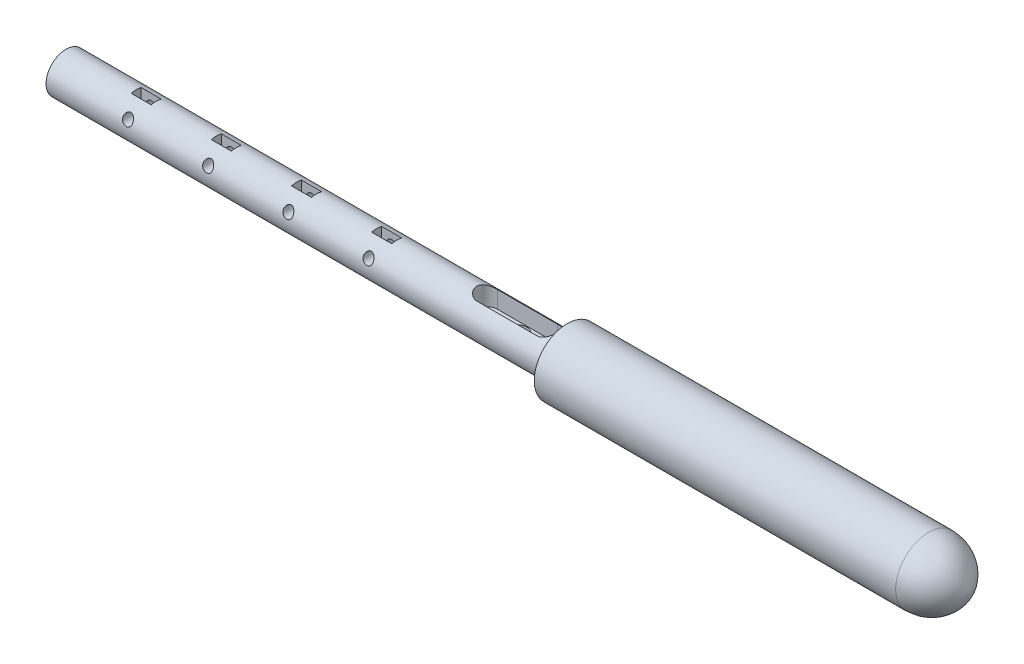
SolidWorks part; units mm, degrees
ref_plane "Front Plane" through (0, 0, 0) normal (0, 0, 1) x (1, 0, 0)
ref_plane "Top Plane" through (0, 0, 0) normal (0, 1, 0) x (1, 0, 0)
ref_plane "Right Plane" through (0, 0, 0) normal (1, 0, 0) x (0, 0, -1)
sketch "Sketch1" plane through (0, 0, 0) normal (1, 0, 0) x (0, 0, -1)
  circle A0 centre (0, 0) radius 3.175
  dimension "D1" = 6.35
extrude "Boss-Extrude1" add sketch "Sketch1" along normal blind 127
sketch "Sketch2" plane through (0, 0, 0) normal (0, 0, 1) x (1, 0, 0)
  line L0 (142.875, 0) -> (79.375, 0)
  line L2 (79.375, 0) -> (79.375, 5.207)
  line L3 (79.375, 5.207) -> (136.6287, 5.207)
  line L4 (0, 3.175) -> (0, -3.175) construction
  arc A0 (136.6287, 5.207) -> (142.875, 0) centre (136.6287, -1.143) cw
  dimension "D1" = 6.35
  dimension "D2" = 5.207
  dimension "D3" = 63.5
  dimension "D4" = 79.375
ref_axis "Axis1" through (127, 0, 0) along (-1, 0, 0)
revolve "Revolve1" add sketch "Sketch2" angle 360 about axis through (127, 0, 0) along (-1, 0, 0)
sketch "Sketch3" plane through (0, 0, 0) normal (-1, 0, 0) x (0, 0, 1)
  line L1 (-0.7938, 3.175) -> (0.7937, 3.175)
  line L2 (-0.7938, 3.175) -> (-0.7937, -3.175)
  line L3 (-0.7937, -3.175) -> (0.7938, -3.175)
  line L4 (0.7937, 3.175) -> (0.7938, -3.175)
  dimension "D1" = 1.5875
  dimension "D2" = 0.7937
  dimension "D3" = 6.35
  dimension "D4" = 3.175
sketch "Sketch4" plane through (0, 0, 0) normal (0, 1, 0) x (1, 0, 0)
  line L1 (76.2, 1.6718) -> (66.675, 1.6718)
  line L2 (0, 3.175) -> (0, -3.175) construction
  line L3 (76.2, -1.5962) -> (66.675, -1.5962)
  arc A0 (66.675, 1.6718) -> (66.675, -1.5962) centre (66.675, 0.0378) ccw
  arc A1 (76.2, 1.6718) -> (76.2, -1.5962) centre (76.2, 0.0378) cw
  dimension "D2" = 9.525
  dimension "D1" = 3.2679
  dimension "D3" = 66.675
extrude "Cut-Extrude2" cut sketch "Sketch4" along normal blind 3.175
hole_wizard "#32 (0.116) Diameter Hole1" positions "Sketch6" profile "Sketch5" hole size "#32" standard "Ansi Inch"
sketch "Sketch6" plane through (0, 0, 0) normal (0, 1, 0) x (-1, 0, 0)
  line L0 (-76.2, -1.6718) -> (-66.675, -1.6718) construction
  arc A0 (-66.675, -1.6718) -> (-66.675, 1.5962) centre (-66.675, -0.0378) ccw construction
  point P0 (-71.4375, -0.0843)
  dimension "D1" = 1.5875
  dimension "D2" = 4.7625
sketch "Sketch5" plane through (71.4375, 0, -0.0843) normal (1, 0, 0) x (0, 0, 1)
  line L0 (0, 0) -> (0, 26.2852)
  line L1 (0, 26.2852) -> (1.4732, 25.4)
  line L2 (1.4732, 25.4) -> (1.4732, 0)
  line L5 (1.4732, 0) -> (0, 0)
  line L10 (0, 26.2852) -> (-1.4732, 25.4) construction
  line L11 (0, -6.35) -> (0, 107.95) construction
  dimension "Hole Dia." = 2.9464
  dimension "Hole Depth" = 25.4
  dimension "Drill Angle" = 118
sketch "Sketch7" plane through (0, 0, 0) normal (0, 0, 1) x (1, 0, 0)
  line L1 (0, 3.175) -> (0, -3.175) construction
  line L2 (127, 0) -> (0, 0) construction
  circle A0 centre (12.7, 1.27) radius 0.7937
  dimension "D1" = 1.5875
  dimension "D2" = 12.7
  dimension "D3" = 1.27
extrude "Cut-Extrude3" cut sketch "Sketch7" against normal blind 5.08 and the other way blind 5.08
ref_axis "Axis2" through (71.4375, -3.175, -0.0843) along (0, 1, 0)
sketch "Sketch9" plane through (0, 0, 0) normal (0, 0, 1) x (1, 0, 0)
  line L0 (71.4375, 4.9906) -> (71.4375, -10.9572) construction
  line L1 (71.4375, -3.175) -> (71.4375, 0) construction
ref_point "Point1"
sketch "Sketch10" plane through (0, 0, 0) normal (0, 1, 0) x (1, 0, 0)
  line L0 (0, 3.175) -> (0, -3.175) construction
  line L1 (11.1125, 0.7938) -> (14.2875, 0.7938)
  line L2 (11.1125, 0.7938) -> (11.1125, -0.7937)
  line L3 (11.1125, -0.7937) -> (14.2875, -0.7937)
  line L4 (14.2875, 0.7938) -> (14.2875, -0.7937)
  line L5 (127, 0) -> (0, 0) construction
  dimension "D1" = 1.5875
  dimension "D2" = 11.1125
  dimension "D3" = 3.175
  dimension "D4" = 0.7937
extrude "Cut-Extrude4" cut sketch "Sketch10" along normal blind 5.715
pattern_linear "LPattern1" count 4 spacing 12.7 along (1, 0, 0) of "Cut-Extrude3", "Cut-Extrude4"
